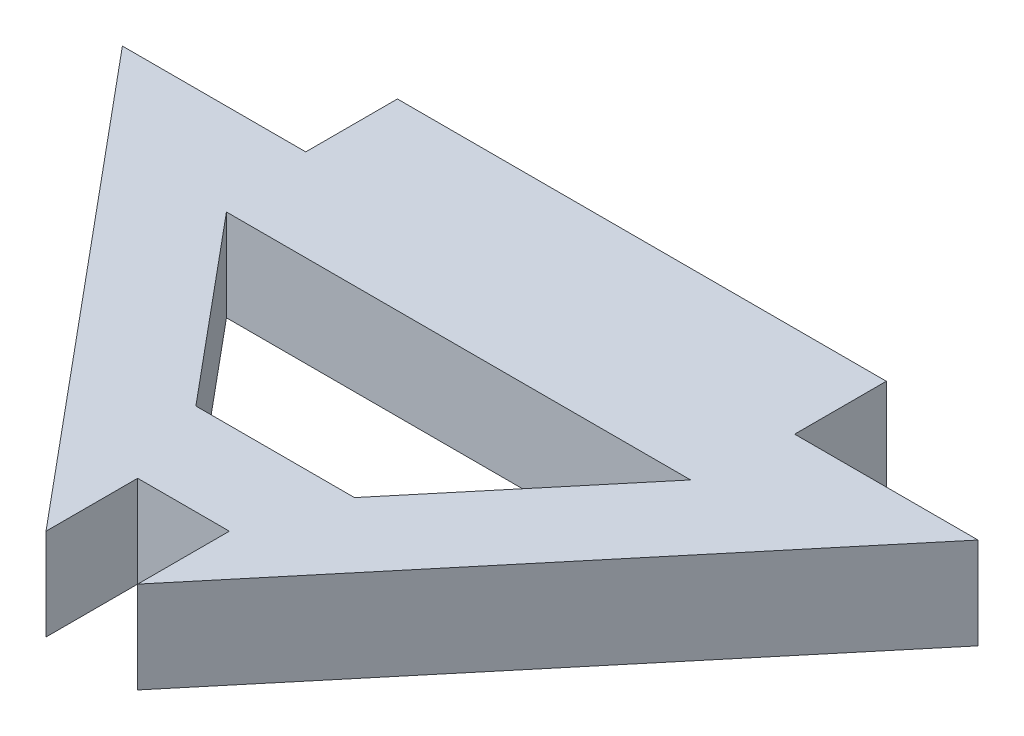
SolidWorks part; units mm, degrees
material "Custom Plastic"
ref_plane "Front Plane" through (0, 0, 0) normal (0, 0, 1) x (1, 0, 0)
ref_plane "Top Plane" through (0, 0, 0) normal (0, 1, 0) x (1, 0, 0)
ref_plane "Right Plane" through (0, 0, 0) normal (1, 0, 0) x (0, 0, -1)
sketch "Sketch1" plane through (0, 0, 0) normal (0, 1, 0) x (1, 0, 0)
  line L0 (22.0795, 3.0287) -> (16.0795, 3.0287)
  line L1 (16.0795, 3.0287) -> (16.0795, 6.0287)
  line L2 (16.0795, 6.0287) -> (0.0795, 6.0287)
  line L3 (0.0795, 6.0287) -> (0.0795, 3.0287)
  line L4 (0.0795, 3.0287) -> (-5.9205, 3.0287)
  line L5 (-5.9205, 3.0287) -> (6.5795, -11.9713)
  line L6 (6.5795, -11.9713) -> (6.5795, -8.9713)
  line L7 (6.5795, -8.9713) -> (9.5795, -8.9713)
  line L8 (9.5795, -8.9713) -> (9.5795, -11.9713)
  line L9 (9.5795, -11.9713) -> (22.0795, 3.0287)
  line L10 (8.0795, 6.0287) -> (8.0795, -8.9713) construction
  line L11 (9.5795, -11.9713) -> (6.5795, -11.9713) construction
  line L12 (15.6744, 0.0287) -> (0.4846, 0.0287)
  line L13 (0.4846, 0.0287) -> (5.4846, -5.9713)
  line L14 (5.4846, -5.9713) -> (10.6744, -5.9713)
  line L15 (10.6744, -5.9713) -> (15.6744, 0.0287)
  point P12 (6.5795, -10.4713)
  dimension "D1" = 3
  dimension "D2" = 28
  dimension "D3" = 3
  dimension "D4" = 6
  dimension "D5" = 12
  dimension "D6" = 3
  dimension "D7" = 3
  dimension "D8" = 3
  dimension "D9" = 3
  dimension "D10" = 3
extrude "Boss-Extrude1" add sketch "Sketch1" along normal blind 3
